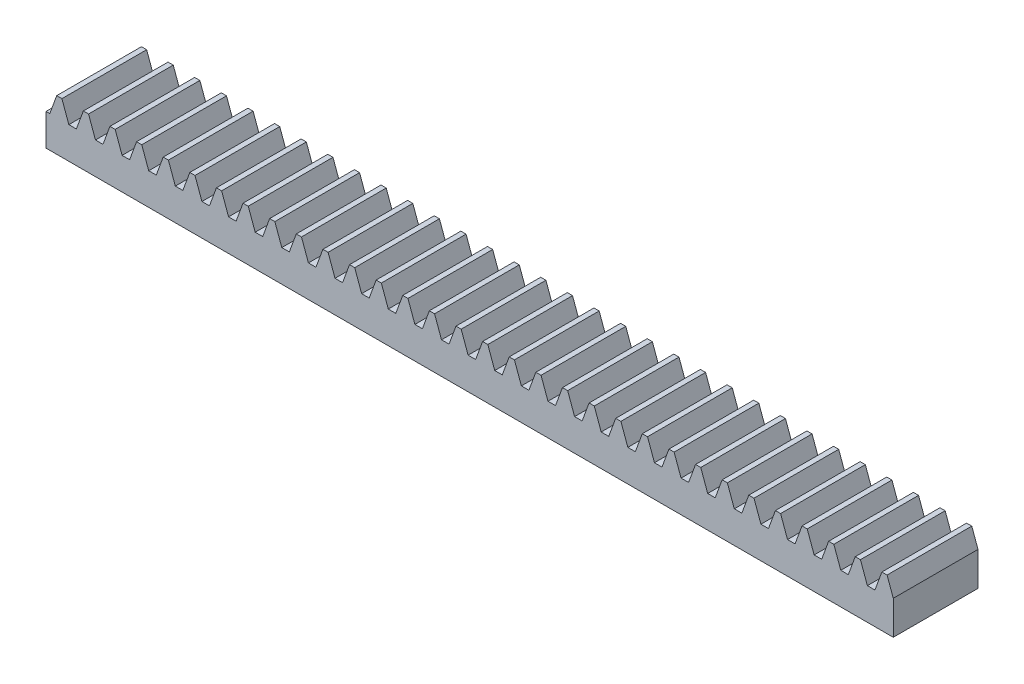
SolidWorks part; units mm, degrees
extrude "Blank" add sketch "BlankSke" against normal blind 10
sketch "BlankSke" plane through (0, 0, 0) normal (0, 0, 1) x (1, 0, 0)
  line L1 (0, 0) -> (100, 0)
  line L2 (0, 0) -> (0, 6)
  line L3 (0, 6) -> (100, 6)
  line L4 (100, 0) -> (100, 6)
  dimension "Length" = 100
ref_plane "Plane1" through (0, 0, 0) normal (0, 0, 1) x (1, 0, 0)
ref_plane "Plane2" through (0, 0, 0) normal (0, 1, 0) x (1, 0, 0)
ref_plane "Plane3" through (0, 0, 0) normal (1, 0, 0) x (0, 0, -1)
other "Configuration Table"
sketch "HoldingSke" plane through (0, 0, 0) normal (0, 1, 0) x (1, 0, 0)
  line L0 (0, 0) -> (0.1392, 0.9903)
  line L1 (-15, 0) -> (100, 0) construction
  line L2 (0, 0) -> (-2.1039, 2.3779)
  line L3 (0, 0) -> (-11.863, 4.5341)
  line L4 (0, 0) -> (7.2428, 4.7035)
  line L5 (0, 0) -> (-23.7986, -8.8762)
  line L6 (0, 0) -> (-10.5278, -7.1032)
  line L9 (-71.009, 38.7566) -> (22.9603, 72.9586)
  line L10 (-76.2, 3.3779) -> (-71.2, 3.3779)
  line L11 (0, 0) -> (-10, 0)
  line L12 (-76.2, 101.6) -> (-76.162, 101.6)
  line L13 (24.9733, 27.94) -> (52.9518, 28.4284)
  line L14 (24.9733, 27.94) -> (24.9743, 27.94)
  line L15 (24.9733, 27.94) -> (100.4006, 29.5858)
  circle A0 centre (0, 0) radius 19.05
  circle A1 centre (0, 0) radius 2.5
  circle A2 centre (0, 0) radius 12.7
  dimension "Num_teeth" = 33
  dimension "Width" = 10
  dimension "Length" = 100
  dimension "Pitch_height" = 5
sketch "TooCutSkeIll" plane through (0, 0, 0) normal (0, 0, 1) x (1, 0, 0)
  line L0 (-1.2538, 5.9737) -> (-0.5045, 3.9152)
  line L1 (-0.2687, 3.75) -> (0.2687, 3.75)
  line L2 (0.5045, 3.9152) -> (1.2538, 5.9737)
  line L3 (100, 6) -> (0, 6) construction
  line L4 (0, 0) -> (0, 64.897) construction
  line L5 (-13.208, 5) -> (12.954, 5) construction
  line L6 (0, 0) -> (100, 0) construction
  line L7 (0.8994, 5) -> (0.8994, 48.7463) construction
  line L8 (-0.8994, 5) -> (-0.8994, 48.7463) construction
  line L9 (1.2914, 6) -> (1.2914, 6.0254)
  line L10 (-1.2914, 6) -> (-1.2914, 6.0254)
  line L11 (-1.2914, 6.0254) -> (1.2914, 6.0254)
  arc A0 (0.2687, 3.75) -> (0.5045, 3.9152) centre (0.2687, 4.001) ccw
  arc A1 (-0.5045, 3.9152) -> (-0.2687, 3.75) centre (-0.2687, 4.001) ccw
  arc A2 (1.2914, 6) -> (1.2538, 5.9737) centre (1.2914, 5.96) ccw
  arc A3 (-1.2538, 5.9737) -> (-1.2914, 6) centre (-1.2914, 5.96) ccw
  dimension "Addendum_plus" = 1.0254
  dimension "Pitch_height" = 5
  dimension "Pressure_angle" = 20
  dimension "Gap_width" = 1.7988
  dimension "Dedendum" = 1.25
extrude "ToothCutIll" [suppressed] cut sketch "TooCutSkeIll" against normal through all
sketch "TooCutSkeSim" plane through (0, 0, 0) normal (0, 0, 1) x (1, 0, 0)
  line L0 (0.4444, 3.75) -> (-0.4444, 3.75)
  line L1 (1.2726, 6.0254) -> (0.4444, 3.75)
  line L2 (0, 17.4625) -> (0, 53.467) construction
  line L3 (1.2726, 6.0254) -> (-1.2726, 6.0254)
  line L6 (-1.2726, 6.0254) -> (-0.4444, 3.75)
  line L9 (-0.8994, 5) -> (0.8994, 5) construction
  line L10 (0, 0) -> (100, 0) construction
  line L11 (0.8994, 5) -> (0.8994, 53.467) construction
  line L12 (-0.8994, 5) -> (-0.8994, 53.467) construction
  dimension "Addendum_plus" = 1.0254
  dimension "Pitch_height" = 5
  dimension "Pressure_angle" = 20
  dimension "Gap_width" = 1.7988
  dimension "Dedendum" = 1.25
extrude "ToothCutSim" cut sketch "TooCutSkeSim" against normal through all
pattern_linear "TeethCuts" count 33 spacing 3.1416 along (1, 0, 0) of "ToothCutIll", "ToothCutSim"
equation "' \"Module@HoldingSke\" = 6.35"
equation "' \"Num_teeth@HoldingSke\" = 12"
equation "' \"Ap@HoldingSke\" =  20"
equation "' \"Ap@HoldingSke\" = 20"
equation "' \"Width@HoldingSke\" = 0.25 * 25.4"
equation "' \"Show_teeth@HoldingSke\" = 500"
equation "' \"Backlash@HoldingSke\" = 0.009 * 25.4"
equation "' \"Addendum_fac@HoldingSke\" = 1.0"
equation "' \"Dedendum_fac@HoldingSke\" = 1.25"
equation "' \"Dedendum_add@HoldingSke\" = 0.00005 * 25.4"
equation "' \"Clearance_fac@HoldingSke\" = 0.25"
equation "' \"Pitch_height@HoldingSke\" = 1 * 25.4"
equation "' \"Length@HoldingSke\" = 4.71 * 25.4"
equation "\"Pitch@HoldingSke\" = 1 / \"Module@HoldingSke\""
equation "\"MPH@HoldingSke\" = \"Dedendum_fac@HoldingSke\" / \"Pitch@HoldingSke\" + 2 * \"Dedendum_add@HoldingSke\" + 0.002 * 25.4"
equation "\"MPH@HoldingSke\" = ((sgn( \"MPH@HoldingSke\" - \"Pitch_height@HoldingSke\")+1)*( \"MPH@HoldingSke\" - \"Pitch_height@HoldingSke\"))/2 + \"Pitch_height@HoldingSke\""
equation "\"Blank_height@BlankSke\" = \"Pitch_height@HoldingSke\" + \"Addendum_fac@HoldingSke\"  / \"Pitch@HoldingSke\" "
equation "\"Length@BlankSke\" =  \"Length@HoldingSke\""
equation "\"Face_width@Blank\" = \"Width@HoldingSke\""
equation "\"Pressure_angle@TooCutSkeIll\" = \"Ap@HoldingSke\""
equation "\"Addendum_plus@TooCutSkeIll\" =  \"Addendum_fac@HoldingSke\"  / \"Pitch@HoldingSke\" + 0.001 *25.4"
equation "\"Dedendum@TooCutSkeIll\" = \"Dedendum_fac@HoldingSke\"  / \"Pitch@HoldingSke\""
equation "\"Pitch_height@TooCutSkeIll\" =  \"MPH@HoldingSke\""
equation "\"Gap_width@TooCutSkeIll\" = 3.14159265 / 2 / \"Pitch@HoldingSke\" + 6 * \"Backlash@HoldingSke\""
equation "\"Pressure_angle@TooCutSkeSim\" = \"Ap@HoldingSke\""
equation "\"Addendum_plus@TooCutSkeSim\" =  \"Addendum_fac@HoldingSke\"  / \"Pitch@HoldingSke\" + 0.001 * 25.4"
equation "\"Dedendum@TooCutSkeSim\" = \"Dedendum_fac@HoldingSke\"  / \"Pitch@HoldingSke\""
equation "\"Pitch_height@TooCutSkeSim\" =  \"MPH@HoldingSke\""
equation "\"Gap_width@TooCutSkeSim\" = 3.14159265 / 2 / \"Pitch@HoldingSke\" + 6 * \"Backlash@HoldingSke\""
equation "\"Root_fillet@TooCutSkeIll\" = \"Clearance_fac@HoldingSke\" / \"Pitch@HoldingSke\" + \"Dedendum_add@HoldingSke\""
equation "\"Break_rad@TooCutSkeIll\" = 0.02 / \"Pitch@HoldingSke\" * 2"
equation "\"Linear_pitch@TeethCuts\" = 3.14159265 / \"Pitch@HoldingSke\""
equation "\"Num_teeth@HoldingSke\" = int( ( \"Length@HoldingSke\" + 0 ) / (3.14159265 / \"Pitch@HoldingSke\")) + 0.9999  + 1"
equation " \"Num_teeth@TeethCuts\" = int( \"Show_teeth@HoldingSke\" ) + 1"
equation " \"Num_teeth@TeethCuts\" = ((sgn( \"Num_teeth@TeethCuts\" - \"Num_teeth@HoldingSke\" )-1)*( \"Num_teeth@TeethCuts\" - \"Num_teeth@HoldingSke\" ))/-2+ \"Num_teeth@HoldingSke\""
equation " \"Num_teeth@TeethCuts\" = ((sgn( \"Num_teeth@TeethCuts\" - 2.0)+1)*( \"Num_teeth@TeethCuts\" - 2.0))/2 +2.0"
